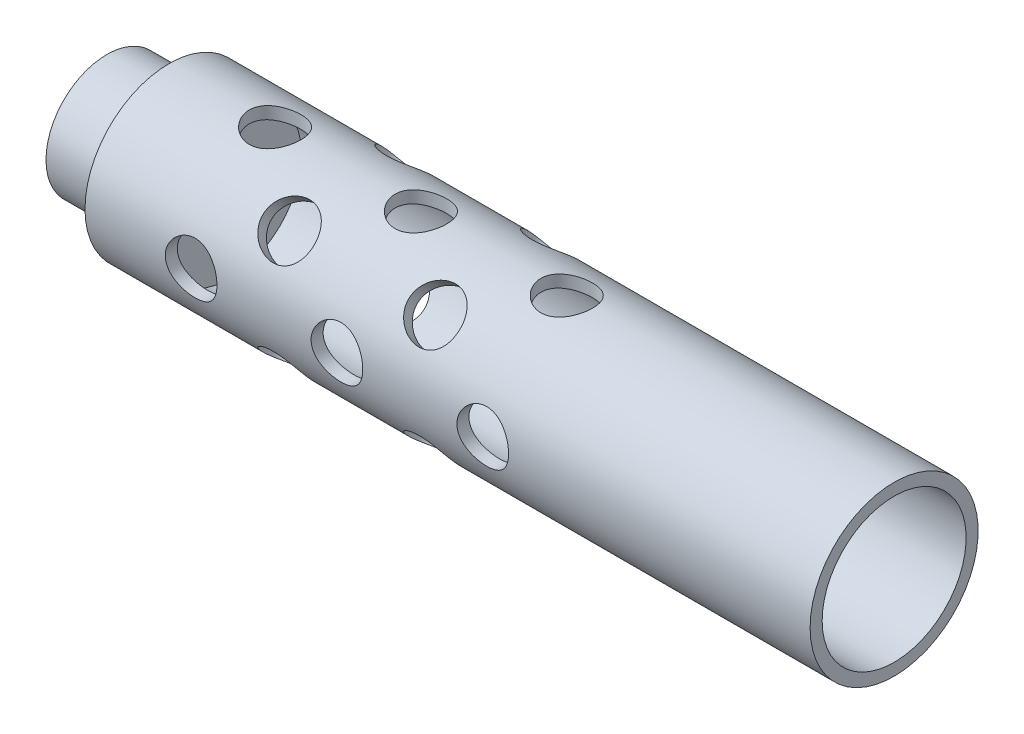
SolidWorks part; units mm, degrees
material "AISI 1045 Steel, cold drawn"
ref_plane "Front Plane" through (0, 0, 0) normal (0, 0, 1) x (1, 0, 0)
ref_plane "Top Plane" through (0, 0, 0) normal (0, 1, 0) x (1, 0, 0)
ref_plane "Right Plane" through (0, 0, 0) normal (1, 0, 0) x (0, 0, -1)
sketch "Sketch1" plane through (0, 0, 0) normal (0, 0, 1) x (1, 0, 0)
  line L0 (-106.62, 0) -> (106.62, 0) construction
  line L1 (-106.62, 0) -> (-106.62, 16.5)
  line L2 (-106.62, 16.5) -> (-89.8, 16.5)
  line L3 (-89.8, 16.5) -> (-89.8, 22.76)
  line L4 (-89.8, 22.76) -> (106.62, 22.76)
  line L5 (106.62, 22.76) -> (106.62, 19.5)
  line L6 (106.62, 19.5) -> (-73.38, 19.5)
  line L7 (-73.38, 19.5) -> (-73.38, 0)
  line L8 (-73.38, 0) -> (-106.62, 0)
  dimension "D1" = 213.24
  dimension "D2" = 16.5
  dimension "D3" = 16.82
  dimension "D4" = 22.76
  dimension "D5" = 19.5
  dimension "D6" = 180
revolve "Revolve1" add sketch "Sketch1" angle 360 about L0
sketch "Sketch3" plane through (0, 0, 0) normal (0, 1, 0) x (1, 0, 0)
  line L0 (106.62, -22.76) -> (106.62, 22.76) construction
  circle A0 centre (17.94, 0) radius 7
  circle A1 centre (-21.56, 0) radius 7
  circle A2 centre (-61.06, 0) radius 7
  dimension "D1" = 14
  dimension "D2" = 88.68
  dimension "D3" = 3
extrude "Cut-Extrude2" cut sketch "Sketch3" against normal blind 50 and the other way blind 50
pattern_circular "CirPattern2" count 4 every 90 about axis through (-89.8, 0, 0) along (-1, 0, 0) of "Cut-Extrude2"
ref_plane "Plane1" through (0, 0, 0) normal (0, 0.7071, -0.7071) x (-1, 0, 0)
sketch "Sketch4" plane through (0, 0, 0) normal (0, 0.7071, -0.7071) x (-1, 0, 0)
  line L2 (-106.62, 22.76) -> (-106.62, -22.76) construction
  circle A0 centre (1.81, 0) radius 7
  circle A1 centre (41.31, 0) radius 7
  dimension "D1" = 14
  dimension "D2" = 108.43
  dimension "D3" = 2
extrude "Cut-Extrude3" cut sketch "Sketch4" against normal blind 50 and the other way blind 50
pattern_circular "CirPattern3" count 4 every 90 about axis through (-89.8, 0, 0) along (-1, 0, 0) of "Cut-Extrude3"
